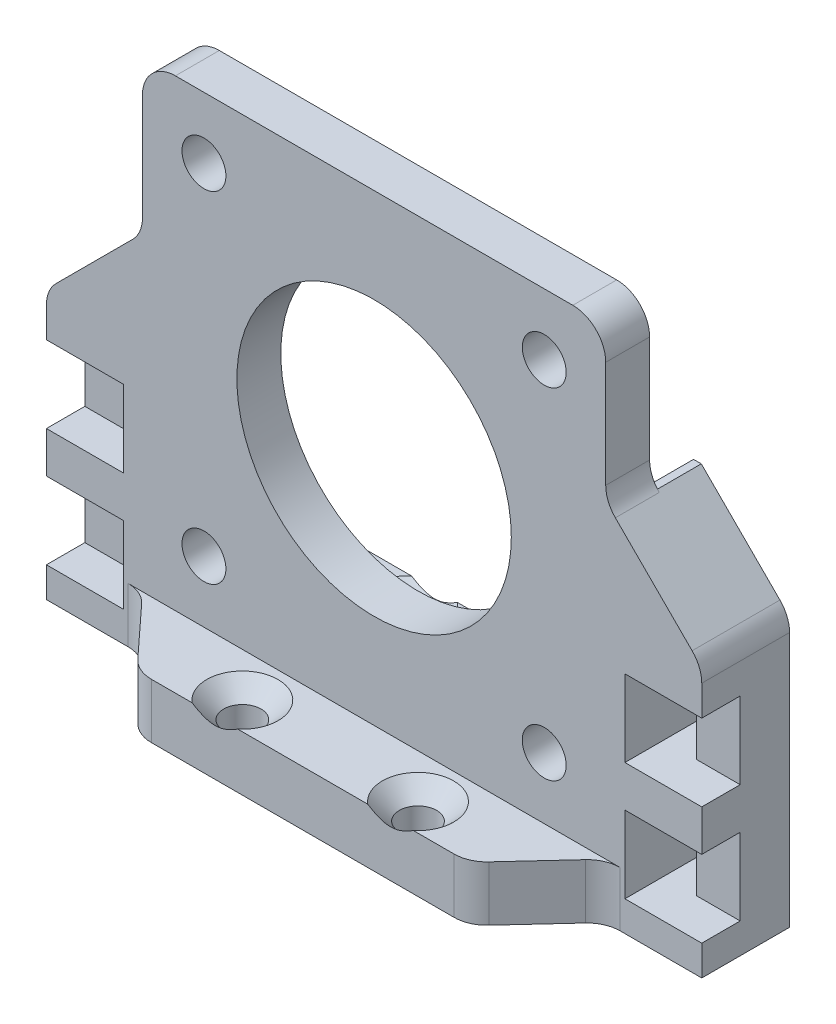
SolidWorks part; units mm, degrees
ref_plane "Front Plane" through (0, 0, 0) normal (0, 0, 1) x (1, 0, 0)
ref_plane "Top Plane" through (0, 0, 0) normal (0, 1, 0) x (1, 0, 0)
ref_plane "Right Plane" through (0, 0, 0) normal (1, 0, 0) x (0, 0, -1)
ref_plane "Plane1" through (0, 0, 1.5) normal (0, 0, 1) x (1, 0, 0)
sketch "Sketch1" plane through (0, 0, 1.5) normal (0, 0, 1) x (1, 0, 0)
  line L1 (-21.1, -21.1) -> (21.1, -21.1)
  line L2 (-21.1, -21.1) -> (-21.1, 21.1)
  line L3 (-21.1, 21.1) -> (21.1, 21.1)
  line L4 (21.1, -21.1) -> (21.1, 21.1)
  line L5 (-21.1, -21.1) -> (21.1, 21.1) construction
  line L6 (-21.1, 21.1) -> (21.1, -21.1) construction
  circle A0 centre (0, 0) radius 12.5
  circle A1 centre (15.5, 15.5) radius 2
  circle A2 centre (15.5, -15.5) radius 2
  circle A3 centre (-15.5, -15.5) radius 2
  circle A4 centre (-15.5, 15.5) radius 2
  point P0 (0, 0)
  point P19 (0, 0)
  dimension "D2" = 25
  dimension "D3" = 4
  dimension "D5" = 31
  dimension "D1" = 42.2
  dimension "D4" = 4
extrude "Boss-Extrude1" add sketch "Sketch1" along normal mid plane 4
sketch "Sketch2" plane through (0, -21.1, 0) normal (0, -1, 0) x (1, 0, 0)
  line L0 (-21.1, -10) -> (21.1, -10)
  line L1 (-21.1, -10) -> (-21.1, 10)
  line L2 (21.1, -10) -> (21.1, 10)
  line L3 (-21.1, 10) -> (21.1, 10)
  line L4 (-21.1, -10) -> (21.1, 10) construction
  line L5 (21.1, -10) -> (-21.1, 10) construction
  line L6 (-21.1, 3.5) -> (-21.1, -0.5) construction
  line L8 (-8, -7.5) -> (8, -7.5) construction
  line L9 (-8, -7.5) -> (-8, 7.5) construction
  line L10 (-8, 7.5) -> (8, 7.5) construction
  line L11 (8, -7.5) -> (8, 7.5) construction
  line L12 (-8, -7.5) -> (8, 7.5) construction
  line L13 (-8, 7.5) -> (8, -7.5) construction
  circle A0 centre (8, 7.5) radius 1.625
  circle A1 centre (8, -7.5) radius 1.625
  circle A2 centre (-8, -7.5) radius 1.625
  circle A3 centre (-8, 7.5) radius 1.625
  point P1 (0, 0)
  point P3 (0, 0)
  dimension "D4" = 3.25
  dimension "D1" = 20
  dimension "D2" = 16
  dimension "D3" = 15
extrude "Boss-Extrude2" add sketch "Sketch2" along normal blind 5
sketch "Sketch3" plane through (0, 0, 0) normal (0, 0, 1) x (1, 0, 0)
  line L0 (-29.85, -2.85) -> (-21.1, -2.85)
  line L1 (-21.1, 21.1) -> (-21.1, -21.1) construction
  line L2 (-29.85, -2.85) -> (-29.85, -26.1)
  line L3 (-29.85, -26.1) -> (-21.1, -26.1)
  line L4 (-29.85, -14.475) -> (-21.1, -14.475) construction
  line L5 (-24.1, -16.35) -> (-24.1, -23.35) construction
  line L6 (0, 0) -> (0, -21.1) construction
  line L7 (21.1, -21.1) -> (-21.1, -21.1) construction
  line L8 (-24.1, -11.35) -> (-24.1, -6.85) construction
  line L9 (-25.35, -11.35) -> (-25.35, -6.85) construction
  line L10 (-22.85, -11.35) -> (-22.85, -6.85) construction
  line L11 (-24.1, -17.6) -> (-24.1, -22.1) construction
  line L12 (-25.35, -17.6) -> (-25.35, -22.1) construction
  line L13 (-22.85, -17.6) -> (-22.85, -22.1) construction
  line L14 (25.35, -5.6) -> (22.85, -5.6)
  line L15 (-21.1, -2.85) -> (-21.1, -26.1)
  line L16 (29.85, -14.475) -> (21.1, -14.475) construction
  line L17 (21.1, -2.85) -> (21.1, -26.1)
  line L18 (29.85, -26.1) -> (21.1, -26.1)
  line L19 (29.85, -2.85) -> (29.85, -26.1)
  line L20 (29.85, -2.85) -> (21.1, -2.85)
  line L21 (22.85, -12.6) -> (22.85, -5.6)
  line L24 (25.35, -12.6) -> (22.85, -12.6)
  line L27 (21.1, -26.1) -> (-21.1, -26.1) construction
  line L28 (-25.35, -12.6) -> (-22.85, -12.6)
  line L29 (-25.35, -12.6) -> (-25.35, -5.6)
  line L30 (-25.35, -5.6) -> (-22.85, -5.6)
  line L31 (-22.85, -12.6) -> (-22.85, -5.6)
  line L32 (-25.35, -12.6) -> (-22.85, -5.6) construction
  line L33 (-25.35, -5.6) -> (-22.85, -12.6) construction
  line L34 (-25.35, -23.35) -> (-22.85, -23.35)
  line L35 (-25.35, -23.35) -> (-25.35, -16.35)
  line L36 (-25.35, -16.35) -> (-22.85, -16.35)
  line L37 (-22.85, -23.35) -> (-22.85, -16.35)
  line L38 (-25.35, -23.35) -> (-22.85, -16.35) construction
  line L39 (-25.35, -16.35) -> (-22.85, -23.35) construction
  line L40 (25.35, -12.6) -> (25.35, -5.6)
  line L41 (25.35, -16.35) -> (22.85, -16.35)
  line L42 (22.85, -23.35) -> (22.85, -16.35)
  line L43 (25.35, -23.35) -> (22.85, -23.35)
  line L44 (25.35, -23.35) -> (25.35, -16.35)
  arc A0 (-25.35, -11.35) -> (-22.85, -11.35) centre (-24.1, -11.35) ccw construction
  arc A1 (-22.85, -6.85) -> (-25.35, -6.85) centre (-24.1, -6.85) ccw construction
  arc A2 (-25.35, -17.6) -> (-22.85, -17.6) centre (-24.1, -17.6) cw construction
  arc A3 (-22.85, -22.1) -> (-25.35, -22.1) centre (-24.1, -22.1) cw construction
  point P18 (-24.1, -9.1)
  point P25 (-24.1, -19.85)
  point P33 (-24.1, -9.1)
  point P56 (-24.1, -19.85)
  dimension "D3" = 1.25
  dimension "D1" = 6.25
  dimension "D2" = 7
  dimension "D4" = 10.75
  dimension "D5" = 4.5
  dimension "D6" = 3
extrude "Boss-Extrude3" add sketch "Sketch3" along direction (0, 0, -1) on the side against the normal blind 2 and the other way up to surface (3.5 mm away) other way up to face at (0, 0, 3.5)
sketch "Sketch4" plane through (0, 0, 3.5) normal (0, 0, 1) x (1, 0, 0)
  line L6 (-25.35, -5.6) -> (-29.85, -5.6)
  line L7 (-29.85, -2.85) -> (-29.85, -26.1) construction
  line L12 (0, 0) -> (0, -6.5728) construction
  line L23 (-29.85, -5.6) -> (-29.85, -12.6)
  line L24 (-29.85, -12.6) -> (-25.35, -12.6)
  line L25 (-25.35, -5.6) -> (-25.35, -12.6) construction
  line L26 (-25.35, -5.6) -> (-25.35, -12.6)
  line L27 (-25.35, -23.35) -> (-22.85, -23.35) construction
  line L28 (-25.35, -16.35) -> (-29.85, -16.35)
  line L29 (-25.35, -16.35) -> (-25.35, -23.35)
  line L30 (-25.35, -23.35) -> (-29.85, -23.35)
  line L31 (-29.85, -16.35) -> (-29.85, -23.35)
  line L32 (29.85, -16.35) -> (29.85, -23.35)
  line L33 (25.35, -23.35) -> (29.85, -23.35)
  line L34 (25.35, -16.35) -> (25.35, -23.35)
  line L35 (25.35, -16.35) -> (29.85, -16.35)
  line L36 (25.35, -5.6) -> (25.35, -12.6)
  line L37 (29.85, -12.6) -> (25.35, -12.6)
  line L38 (29.85, -5.6) -> (29.85, -12.6)
  line L39 (25.35, -5.6) -> (29.85, -5.6)
extrude "Cut-Extrude1" cut sketch "Sketch4" against normal up to surface (3.5 mm away) up to plane "Front Plane"
hole_wizard "CSK for M3 Flat Head Machine Screw1" positions "Sketch7" profile "Sketch8" countersink size "M3" standard "ANSI Metric" end condition through all
sketch "Sketch7" plane through (0, -21.1, 0) normal (0, 1, 0) x (1, 0, 0)
  point P0 (-8, -7.5)
  point P3 (8, -7.5)
  point P6 (-8, 7.5)
  point P9 (8, 7.5)
sketch "Sketch8" plane through (-8, -21.1, 7.5) normal (1, 0, 0) x (0, 0, 1)
  line L0 (0, 0) -> (0, 5)
  line L1 (0, 5) -> (1.7, 5)
  line L2 (1.7, 5) -> (1.7, 1.55)
  line L3 (1.7, 1.55) -> (3.25, 0)
  line L5 (3.25, 0) -> (0, 0)
  line L6 (-1.7, 1.55) -> (-3.25, 0) construction
  line L11 (0, -6.35) -> (0, 107.95) construction
  dimension "Thru Hole Dia." = 3.4
  dimension "Thru Hole Depth" = 5
  dimension "Near C'Sink Dia." = 6.5
  dimension "Near C'Sink Angle" = 90
sketch "Sketch10" plane through (0, 0, -0.5) normal (0, 0, -1) x (-1, 0, 0)
  line L0 (21.1, -2.85) -> (21.1, -26.1)
  line L1 (-22.85, -5.6) -> (-22.85, -12.6) construction
  line L5 (29.85, -2.85) -> (29.85, -26.1) construction
  line L6 (21.1, -2.85) -> (29.85, -2.85) construction
  line L7 (29.85, -26.1) -> (21.1, -26.1)
  line L8 (29.85, -2.85) -> (29.85, -26.1)
  line L9 (21.1, -2.85) -> (29.85, -2.85)
  line L10 (0, 0) -> (0, -26.1) construction
  line L11 (21.1, -26.1) -> (-21.1, -26.1) construction
  line L12 (-21.1, -2.85) -> (-29.85, -2.85)
  line L13 (-29.85, -2.85) -> (-29.85, -26.1)
  line L14 (-29.85, -26.1) -> (-21.1, -26.1)
  line L15 (-21.1, -2.85) -> (-21.1, -26.1)
  line L16 (21.1, -26.1) -> (-21.1, -26.1) construction
  line L17 (25.35, -5.6) -> (25.35, -12.6) construction
  line L18 (22.85, -5.6) -> (25.35, -5.6) construction
  line L19 (25.35, -12.6) -> (22.85, -12.6) construction
  line L20 (-22.85, -16.35) -> (-22.85, -23.35) construction
  line L34 (22.85, -16.35) -> (25.35, -16.35) construction
  line L35 (25.35, -16.35) -> (25.35, -23.35) construction
  line L36 (-22.85, -12.6) -> (-25.35, -12.6) construction
  line L37 (-25.35, -12.6) -> (-25.35, -5.6) construction
  line L39 (-22.85, -16.35) -> (-22.85, -23.35)
  line L47 (-22.85, -5.6) -> (-22.85, -12.6)
  line L49 (22.85, -23.35) -> (22.85, -16.35) construction
  line L53 (22.85, -12.6) -> (22.85, -5.6) construction
  line L57 (22.85, -23.35) -> (22.85, -16.35)
  line L61 (22.85, -12.6) -> (22.85, -5.6)
  line L65 (-25.35, -5.6) -> (-22.85, -5.6) construction
  line L66 (-25.35, -23.35) -> (-25.35, -16.35) construction
  line L67 (-25.35, -16.35) -> (-22.85, -16.35) construction
  line L68 (-22.85, -23.35) -> (-25.35, -23.35) construction
  line L69 (-25.35, -23.35) -> (-25.35, -16.35)
  line L70 (-22.85, -23.35) -> (-25.35, -23.35)
  line L71 (-25.35, -16.35) -> (-22.85, -16.35)
  line L72 (-25.35, -5.6) -> (-22.85, -5.6)
  line L73 (-25.35, -12.6) -> (-25.35, -5.6)
  line L74 (-22.85, -12.6) -> (-25.35, -12.6)
  line L75 (25.35, -16.35) -> (25.35, -23.35)
  line L76 (22.85, -16.35) -> (25.35, -16.35)
  line L77 (25.35, -12.6) -> (22.85, -12.6)
  line L78 (22.85, -5.6) -> (25.35, -5.6)
  line L79 (25.35, -5.6) -> (25.35, -12.6)
  line L80 (25.35, -23.35) -> (22.85, -23.35) construction
  line L81 (25.35, -23.35) -> (22.85, -23.35)
  point P15 (21, -26)
  line M35 (21.1, -2.85) -> (21.1, 21.1)
  line M36 (-21.1, 21.1) -> (-21.1, -2.85)
extrude "Boss-Extrude4" add sketch "Sketch10" along normal blind 4 contours L15 M36 | L0 M35 region at (-25.7607, -14.475, -0.5) region at (25.7607, -14.475, -0.5)
sketch "Sketch11" plane through (0, -21.1, 0) normal (0, 1, 0) x (1, 0, 0)
  line L1 (-29.85, -3.5) -> (-21.1, -3.5) construction
  line L4 (0, 0) -> (-21, 0) construction
  line L6 (0, 0) -> (0, 10) construction
  line L7 (-5.9233, 10) -> (5.9233, 10) construction
  line L11 (-21.1, -10) -> (-21.1, -3.5)
  line L12 (-15.1, -10) -> (-21.1, -10)
  line L13 (-21.1, -3.5) -> (-15.1, -10)
  line L17 (-21.1, 4.5) -> (-15.1, 10)
  line L18 (-21.1, 10) -> (-10.0767, 10) construction
  line L19 (-15.1, 10) -> (-21.1, 10)
  line L20 (-21.1, 10) -> (-21.1, 4.5)
  line L21 (-21.1, -10) -> (-21.1, -3.5) construction
  line L22 (-10.0767, -10) -> (-21.1, -10) construction
  line L24 (15.1, -10) -> (21.1, -10)
  line L25 (21.1, -3.5) -> (15.1, -10)
  line L26 (21.1, -10) -> (21.1, -3.5)
  line L27 (21.1, 10) -> (21.1, 4.5)
  line L28 (15.1, 10) -> (21.1, 10)
  line L29 (21.1, 4.5) -> (15.1, 10)
  line L30 (21.1, -3.5) -> (15.1, -10)
  line L31 (15.1, -10) -> (21.1, -10)
  line L32 (21.1, -10) -> (21.1, -3.5)
  line L33 (-21.1, 4.5) -> (-29.85, 4.5) construction
  point P2 (0, 0)
  point P6 (0, 0)
  point P9 (0, 0)
  point P10 (-21, -3)
  point P23 (0, 0)
  point P28 (-21, 5)
  line M8 (-10.0767, 10) -> (-21.1, 10)
  line M9 (-21.1, 10) -> (-21.1, 4.5)
  line M11 (21.1, 4.5) -> (21.1, 10)
  line M12 (21.1, 10) -> (10.0767, 10)
  dimension "D1" = 6
extrude "Cut-Extrude3" cut sketch "Sketch11" against normal blind 10 contours L13 L11 L12 | L24 L26 L25 | L17 M9 M8 | L29 M11 M12 region at (-19.1, -21.1, 7.8333) region at (-19.1, -21.1, -8.1667) region at (19.1, -21.1, 7.8333) region at (19.1, -21.1, -8.1667)
chamfer "Chamfer1" distance 10 angle 45 2 edges at (-21.1, -2.85, 1.5) (21.1, -2.85, 1.5)
fillet "Fillet2" radius 3 4 edges at (29.85, -1.6, -0.5) (21.1, 7.15, 1.5) (-29.85, -1.6, -0.5) (-21.1, 7.15, 1.5)
fillet "Fillet3" radius 3 2 edges at (21.1, 21.1, 1.5) (-21.1, 21.1, 1.5)
fillet "Fillet4" radius 3 8 edges at (-15.1, -23.6, 10) (15.1, -23.6, 10) (15.1, -23.6, -10) (-15.1, -23.6, -10) (-21.1, -23.6, -4.5) (21.1, -23.6, -4.5) (21.1, -23.6, 3.5) (-21.1, -23.6, 3.5)
chamfer "Chamfer2" distance 1 angle 45 2 edges at (-21.1, 7.15, -2.5) (21.1, 7.15, -2.5) first distance on face at (-24.0167, 4.2333, -0.5) first distance on face at (24.0167, 4.2333, -0.5)
chamfer "Chamfer3" distance 0.5 angle 45 4 edges at (-25.35, -9.1, 0) (-25.35, -19.85, 0) (25.35, -19.85, 0) (25.35, -9.1, 0)
sketch "Sketch12" plane through (0, -23.35, 0) normal (0, 1, 0) x (1, 0, 0)
  line L0 (-25.85, 0) -> (-29.85, 0) construction
  line L1 (-25.35, 0.5) -> (-25.35, 4.5) construction
  line L2 (-25.85, 0) -> (-29.85, 0) construction
  line L3 (-25.35, 0.5) -> (-25.35, 4.5) construction
  line L4 (-26.35, 0.5) -> (-26.35, 0)
  line L5 (-26.35, 0) -> (-25.85, 0)
  line L6 (-25.85, 1) -> (-25.35, 1)
  line L7 (-25.35, 1) -> (-25.35, 0.5)
  arc A0 (-25.85, 1) -> (-26.35, 0.5) centre (-25.85, 0.5) ccw
  arc A1 (-25.85, 0) -> (-25.35, 0.5) centre (-25.85, 0.5) ccw
extrude "Cut-Extrude4" [suppressed] cut sketch "Sketch12" against normal through all both and the other way through all contours A0 L4 L5 A1 L7 L6
